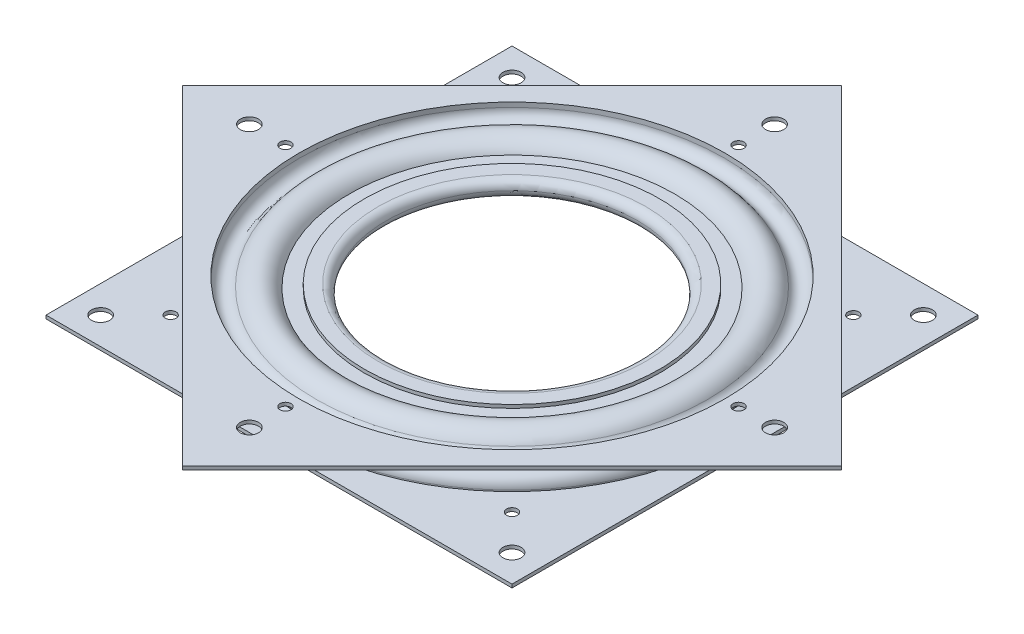
SolidWorks part; units mm, degrees
note: The reader was unsure of these and kept them because the rebuilt part matched: shared geometry of "Sketch1<5>".
ref_plane "Front" through (0, 0, 0) normal (0, 0, 1) x (1, 0, 0)
ref_plane "Top" through (0, 0, 0) normal (0, 1, 0) x (1, 0, 0)
ref_plane "Right" through (0, 0, 0) normal (1, 0, 0) x (0, 0, -1)
sketch "Sketch1" plane through (0, 0, 0) normal (0, 0, 1) x (1, 0, 0)
  line L0 (0, 21.7127) -> (0, -25.7345) construction
  line L1 (32.1955, 1.778) -> (29.21, 1.778)
  line L2 (29.21, -1.778) -> (35.181, -1.778)
  line L3 (29.21, 1.0414) -> (35.474, 1.0414)
  line L4 (46.4273, -3.81) -> (46.4273, -4.826)
  line L5 (46.4273, -4.826) -> (50.8, -4.826)
  line L6 (-2.2827, 0) -> (4.7936, 0) construction
  line L7 (46.4273, 2.286) -> (46.4273, 3.302)
  line L8 (46.4273, 3.302) -> (50.8, 3.302)
  arc A0 (29.21, 1.778) -> (29.21, -1.778) centre (29.21, 0) ccw
  arc A1 (35.181, -1.778) -> (42.6355, -2.794) centre (39.116, -0.762) ccw
  arc A2 (42.6355, -2.794) -> (46.4273, -3.81) centre (44.3953, -3.81) cw
  circle A3 centre (39.116, -0.762) radius 4.064 construction
  arc A4 (35.474, 1.0414) -> (42.6355, 1.27) centre (39.116, -0.762) cw
  arc A5 (42.6355, 1.27) -> (46.4273, 2.286) centre (44.3953, 2.286) ccw
  point P14 (32.1955, -1.778)
  dimension "D1" = 54.864
  dimension "D5" = 8.128
  dimension "D7" = 4.064
  dimension "D6" = 78.232
  dimension "D2" = 3.556
  dimension "D3" = 101.6
  dimension "D4" = 6.604
  dimension "D8" = 0.7366
  dimension "D9" = 8.128
revolve "Revolve-Thin4" add sketch "Sketch1" angle 360 about L0
revolve "Revolve-Thin5" add sketch "Sketch1<5>" angle 360 about L0
sketch "Sketch1<5>" plane through (0, 0, 0) normal (0, 0, 1) x (1, 0, 0) same geometry as "Sketch1"
sketch "Sketch2" plane through (0, -4.826, 0) normal (0, -1, 0) x (1, 0, 0)
  line L0 (50.8, 50.8) -> (50.8, -50.8)
  line L1 (50.8, -50.8) -> (-50.8, -50.8)
  line L2 (50.8, 50.8) -> (-50.8, 50.8)
  line L3 (-50.8, 50.8) -> (-50.8, -50.8)
  circle A0 centre (0, 0) radius 46.4273
  circle A1 centre (0, 0) radius 46.4273 construction
  circle A4 centre (0, 0) radius 50.8 construction
extrude "Extrude1" add sketch "Sketch2" against normal up to surface (0.7366 mm away) up to face at (0, -4.0894, 50.8)
sketch "Sketch3" plane through (0, 3.302, 0) normal (0, 1, 0) x (-1, 0, 0)
  line L1 (0, -71.842) -> (71.842, 0)
  line L2 (0, -71.842) -> (-71.842, 0)
  line L3 (-71.842, 0) -> (0, 71.842)
  line L4 (71.842, 0) -> (0, 71.842)
  circle A0 centre (0, 0) radius 50.8 construction
  circle A1 centre (0, 0) radius 46.4273
  circle A2 centre (0, 0) radius 46.4273 construction
extrude "Extrude2" add sketch "Sketch3" against normal up to surface (0.7366 mm away) up to face at (0, 2.5654, 50.8)
sketch "Sketch4" plane through (0, 0, 0) normal (0, 0, 1) x (1, 0, 0)
  line L0 (39.116, 2.5146) -> (39.116, -4.0386)
  line L1 (26.6717, 2.5146) -> (28.1604, 2.5146) construction
  line L2 (71.842, 2.5654) -> (0, 2.5654) construction
  line L3 (39.116, 2.8375) -> (39.116, -4.9447) construction
  arc A0 (39.116, -4.0386) -> (39.116, 2.5146) centre (39.116, -0.762) ccw
  circle A1 centre (39.116, -0.762) radius 4.064 construction
  dimension "D1" = 0.0508
revolve "Revolve1" add sketch "Sketch4" angle 360 about L3
pattern_circular "CirPattern1" count 4 over 360 about axis through (0, 0, 0) along (0, 1, 0) of bodies 113
hole_wizard "5/32 (0.156250) Diameter Hole1" positions "Sketch6" profile "Sketch5" hole size "5/32" standard "Ansi Inch" end condition through all
sketch "Sketch6" plane through (0, -4.0894, 0) normal (0, 1, 0) x (-1, 0, 0)
  line L0 (0, -4.6477) -> (0, 4.6477) construction
  line L1 (4.7889, 0) -> (-4.7889, 0) construction
  line L2 (50.8, -50.8) -> (-50.8, -50.8) construction
  line L3 (-50.8, -50.8) -> (-50.8, 50.8) construction
  point P0 (-44.8437, -44.8437)
  point P1 (-44.8437, 44.8437)
  point P2 (44.8437, -44.8437)
  point P3 (44.8437, 44.8437)
  dimension "D1" = 89.6874
  dimension "D2" = 89.6874
sketch "Sketch5" plane through (44.8437, -4.0894, -44.8437) normal (1, 0, 0) x (0, 0, 1)
  line L0 (0, 0) -> (0, 0.7366)
  line L1 (0, 0.7366) -> (1.9844, 0.7366)
  line L2 (1.9844, 0.7366) -> (1.9844, 0)
  line L5 (1.9844, 0) -> (0, 0)
  line L11 (0, -6.35) -> (0, 107.95) construction
  dimension "Thru Hole Dia." = 3.9688
  dimension "Thru Hole Depth" = 0.7366
hole_wizard "5/32 (0.156250) Diameter Hole2" positions "Sketch8" profile "Sketch7" hole size "5/32" standard "Ansi Inch" end condition through all
sketch "Sketch8" plane through (0, 3.302, 0) normal (0, 1, 0) x (-1, 0, 0)
  line L0 (-5.1708, 5.1708) -> (5.1708, -5.1708) construction
  line L1 (5.9484, 5.9484) -> (-5.9484, -5.9484) construction
  line L2 (0, 71.842) -> (-71.842, 0) construction
  point P0 (-57.2581, 0)
  point P5 (0, -57.2581)
  point P7 (57.2581, 0)
  point P8 (0, 57.2581)
  dimension "D1" = 80.9752
  dimension "D2" = 80.9752
sketch "Sketch7" plane through (57.2581, 3.302, 0) normal (1, 0, 0) x (0, 0, 1)
  line L0 (0, 0) -> (0, 8.128)
  line L1 (0, 8.128) -> (1.9844, 8.128)
  line L2 (1.9844, 8.128) -> (1.9844, 0)
  line L5 (1.9844, 0) -> (0, 0)
  line L11 (0, -6.35) -> (0, 107.95) construction
  dimension "Thru Hole Dia." = 3.9688
  dimension "Thru Hole Depth" = 8.128
hole_wizard "3/32 (0.093750) Diameter Hole1" positions "Sketch10" profile "Sketch9" hole size "3/32" standard "Ansi Inch" end condition up to next
sketch "Sketch10" plane through (0, 3.302, 0) normal (0, 1, 0) x (-1, 0, 0)
  line L0 (8.7476, -8.7476) -> (-8.7476, 8.7476) construction
  line L1 (-4.5488, -4.5488) -> (4.5488, 4.5488) construction
  line L2 (-71.842, 0) -> (0, -71.842) construction
  point P0 (0, -49.3914)
  point P1 (-49.3914, 0)
  point P2 (0, 49.3914)
  point P3 (49.3914, 0)
  dimension "D1" = 69.85
  dimension "D2" = 69.85
sketch "Sketch9" plane through (0, 3.302, -49.3914) normal (1, 0, 0) x (0, 0, 1)
  line L0 (0, 0) -> (0, 0.7366)
  line L1 (0, 0.7366) -> (1.1906, 0.7366)
  line L2 (1.1906, 0.7366) -> (1.1906, 0)
  line L5 (1.1906, 0) -> (0, 0)
  line L11 (0, -6.35) -> (0, 107.95) construction
  dimension "Thru Hole Dia." = 2.3812
  dimension "Thru Hole Depth" = 0.7366
hole_wizard "3/32 (0.093750) Diameter Hole2" positions "Sketch12" profile "Sketch11" hole size "3/32" standard "Ansi Inch"
sketch "Sketch12" plane through (0, -4.0894, 0) normal (0, 1, 0) x (-1, 0, 0)
  line L0 (0, 10.5411) -> (0, -10.5411) construction
  line L1 (-13.1958, 0) -> (13.1958, 0) construction
  line L2 (-50.8, 50.8) -> (50.8, 50.8) construction
  point P0 (-37.211, 37.211)
  point P1 (37.211, 37.211)
  point P2 (37.211, -37.211)
  point P3 (-37.211, -37.211)
  dimension "D1" = 74.422
  dimension "D2" = 74.422
sketch "Sketch11" plane through (37.211, -4.0894, 37.211) normal (1, 0, 0) x (0, 0, 1)
  line L0 (0, 0) -> (0, 26.1154)
  line L1 (0, 26.1154) -> (1.1906, 25.4)
  line L2 (1.1906, 25.4) -> (1.1906, 0)
  line L5 (1.1906, 0) -> (0, 0)
  line L10 (0, 26.1154) -> (-1.1906, 25.4) construction
  line L11 (0, -6.35) -> (0, 107.95) construction
  dimension "Hole Dia." = 2.3812
  dimension "Hole Depth" = 25.4
  dimension "Drill Angle" = 118
split line "Split Line1"
equation "\"D7@Sketch1\"=\"D5@Sketch1\"/2"
equation "\"D6@Sketch1\" = (\"D1@Sketch1\"+\"D3@Sketch1\")/2"
equation "\"D5@Sketch1\"=\"D9@Sketch1\""
